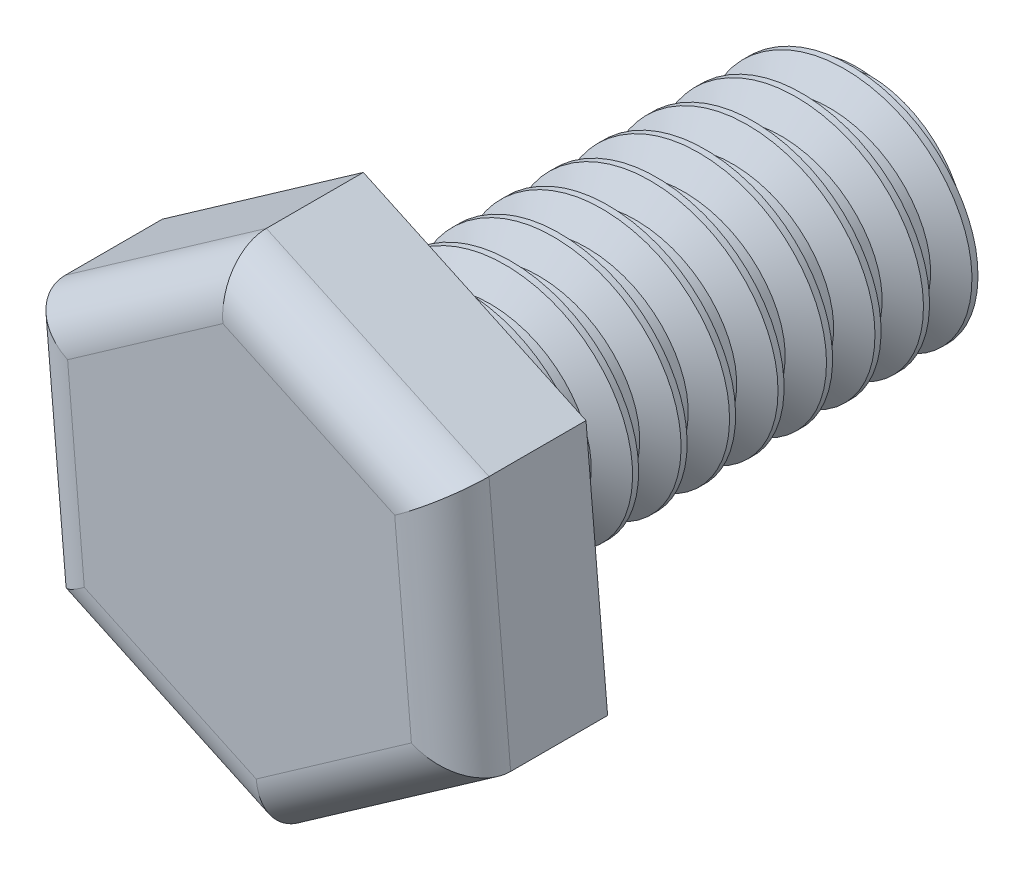
SolidWorks part; units mm, degrees
ref_plane "Front Plane" through (0, 0, 0) normal (0, 0, 1) x (1, 0, 0)
ref_plane "Top Plane" through (0, 0, 0) normal (0, 1, 0) x (1, 0, 0)
ref_plane "Right Plane" through (0, 0, 0) normal (1, 0, 0) x (0, 0, -1)
sketch "Sketch1" plane through (0, 0, 0) normal (0, 0, 1) x (1, 0, 0)
  circle A0 centre (0, 0) radius 2
  dimension "D1" = 4
extrude "Boss-Extrude1" add sketch "Sketch1" along normal blind 10
sketch "Sketch2" plane through (0, 0, 10) normal (0, 0, 1) x (1, 0, 0)
  circle A0 centre (0, 0) radius 5.0654
extrude "Boss-Extrude2" add sketch "Sketch2" along normal blind 3
sketch "Sketch3" plane through (0, 0, 13) normal (0, 0, 1) x (1, 0, 0)
  line L1 (4.5927, -2.1367) -> (4.1468, 2.909)
  line L2 (4.1468, 2.909) -> (-0.4459, 5.0457)
  line L3 (-0.4459, 5.0457) -> (-4.5927, 2.1367)
  line L4 (-4.5927, 2.1367) -> (-4.1468, -2.909)
  line L5 (-4.1468, -2.909) -> (0.4459, -5.0457)
  line L6 (0.4459, -5.0457) -> (4.5927, -2.1367)
  circle A0 centre (0, 0) radius 4.3868 construction
extrude "Cut-Extrude1" cut sketch "Sketch3" against normal blind 3 flip side to cut
fillet "Fillet1" radius 1 6 edges at (-4.3697, -0.3861, 13) (-2.5193, 3.5912, 13) (1.8505, 3.9774, 13) (4.3697, 0.3861, 13) (2.5193, -3.5912, 13) (-1.8505, -3.9774, 13)
thread "Thread1" pitch 1 method extrude profile "Thread Profile2" start angle 0, offset 1, length 11, pitch 1, diameter 4
ref_plane "Plane2" through (2, 0, -1) normal (0, -1, 0) x (1, 0, 0)
sketch "Thread Profile2" plane through (2, 0, -1) normal (0, -1, 0) x (1, 0, 0)
  line L0 (0, 0) -> (0, 1) construction
  line L1 (0, 0) -> (0.5413, 0.3125)
  line L2 (0.5413, 0.3125) -> (0.5413, 0.4375)
  line L3 (0.5413, 0.4375) -> (0, 0.75)
  line L4 (0.5413, 0.375) -> (0, 0.375) construction
  line L11 (0, 0) -> (0, 0.75)
  point P2 (0, 0)
  dimension "Pitch" = 1
  dimension "Profile_Angle" = 60
  dimension "Profile_Land" = 0.125
  dimension "Profile_Height" = 0.5413
sketch "Sketch8" plane through (0, 0, 0) normal (0, 0, -1) x (-1, 0, 0)
  circle A0 centre (0, 0) radius 3.9882
extrude "Cut-Extrude2" cut sketch "Sketch8" along normal blind 3
